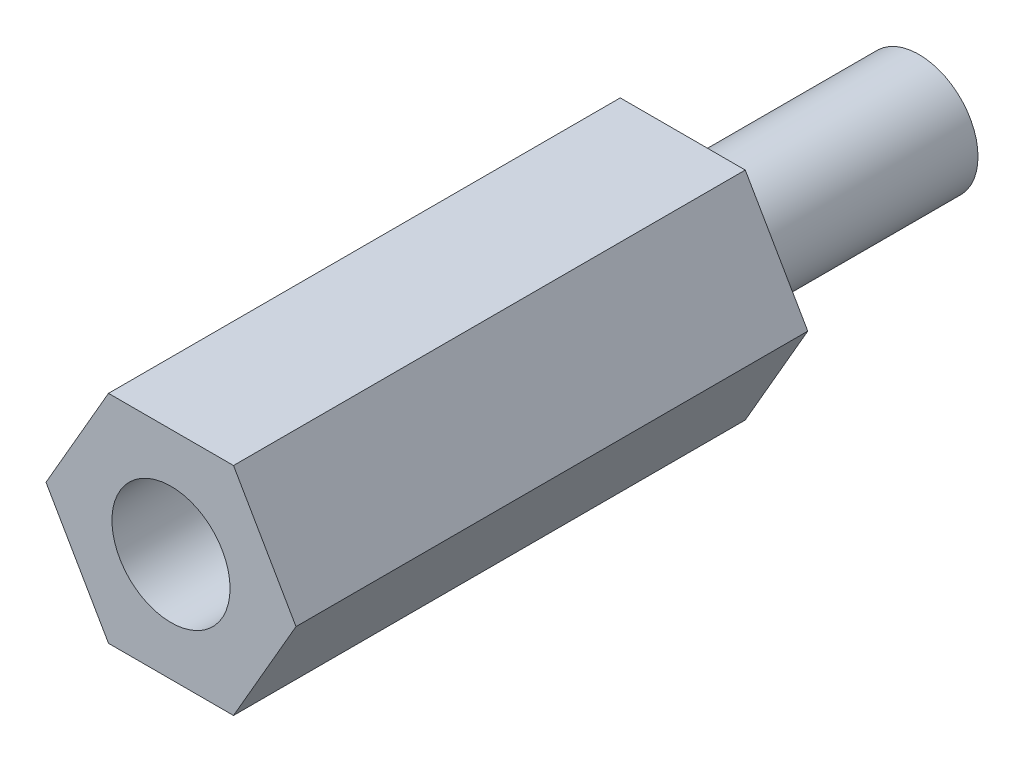
SolidWorks part; units mm, degrees
ref_plane "Front Plane" through (0, 0, 0) normal (0, 0, 1) x (1, 0, 0)
ref_plane "Top Plane" through (0, 0, 0) normal (0, 1, 0) x (1, 0, 0)
ref_plane "Right Plane" through (0, 0, 0) normal (1, 0, 0) x (0, 0, -1)
sketch "Sketch1" plane through (0, 0, 0) normal (0, 0, 1) x (1, 0, 0)
  line L1 (1.5877, -2.75) -> (3.1754, 0)
  line L2 (3.1754, 0) -> (1.5877, 2.75)
  line L3 (1.5877, 2.75) -> (-1.5877, 2.75)
  line L4 (-1.5877, 2.75) -> (-3.1754, 0)
  line L5 (-3.1754, 0) -> (-1.5877, -2.75)
  line L6 (-1.5877, -2.75) -> (1.5877, -2.75)
  circle A0 centre (0, 0) radius 1.5
  circle A1 centre (0, 0) radius 2.75 construction
  dimension "D1" = 5.5
  dimension "D2" = 3
extrude "Boss-Extrude1" add sketch "Sketch1" along normal blind 13 contours L3 L4 L5 L6 L1 L2
extrude "Boss-Extrude2" add sketch "Sketch1<3>" against normal blind 6 contours A0
sketch "Sketch1<3>" plane through (0, 0, 0) normal (0, 0, 1) x (1, 0, 0) same geometry as "Sketch1"
extrude "Cut-Extrude1" cut sketch "Sketch1<4>" against normal blind 6 from surface contours A0 starting at face at (0, 0, 13)
sketch "Sketch1<4>" plane through (0, 0, 0) normal (0, 0, 1) x (1, 0, 0) same geometry as "Sketch1"
